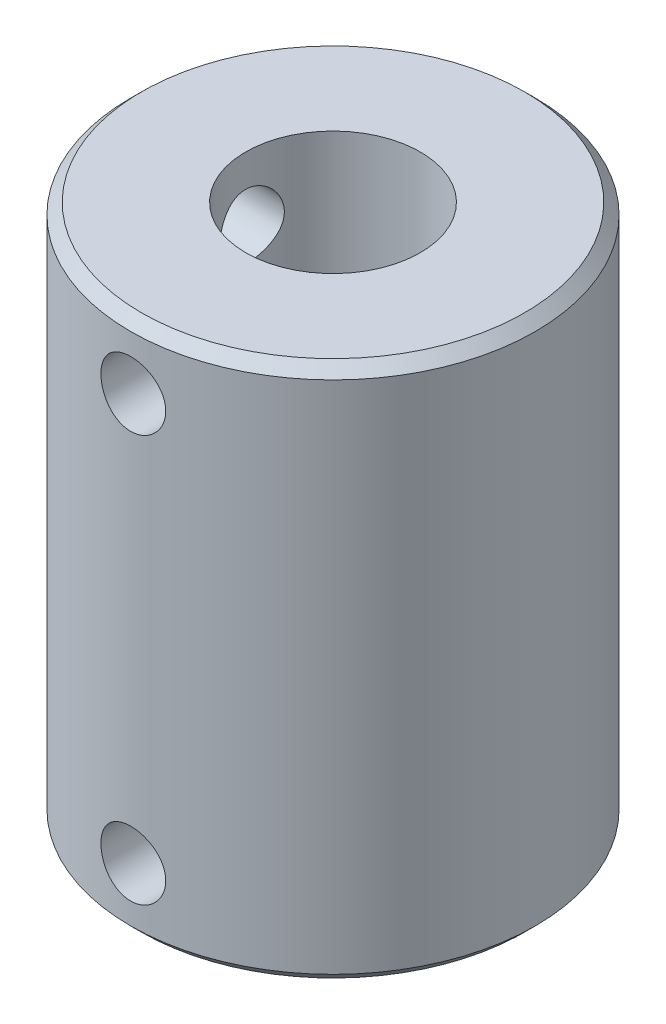
SolidWorks part; units mm, degrees
ref_plane "Front Plane" through (0, 0, 0) normal (0, 0, 1) x (1, 0, 0)
ref_plane "Top Plane" through (0, 0, 0) normal (0, 1, 0) x (1, 0, 0)
ref_plane "Right Plane" through (0, 0, 0) normal (1, 0, 0) x (0, 0, -1)
sketch "Sketch1" plane through (0, 0, 0) normal (0, 1, 0) x (1, 0, 0)
  circle A0 centre (0, 0) radius 9.36
  dimension "D1" = 18.72
extrude "Boss-Extrude1" add sketch "Sketch1" along normal blind 24.82
sketch "Sketch2" plane through (0, 0, 0) normal (0, 1, 0) x (1, 0, 0)
  circle A0 centre (0, 0) radius 2.545
  circle A1 centre (0, 0) radius 4.04
  dimension "D1" = 5.09
  dimension "D2" = 8.08
extrude "Cut-Extrude1" cut sketch "Sketch2" along normal through all contours A0 region at (0, 0, 0)
extrude "Cut-Extrude2" cut sketch "Sketch2<3>" against normal blind 18.28 from surface contours A1 A0 region at (-3.9257, 0, 0) starting at face at (0, 24.82, 2.545)
sketch "Sketch2<3>" plane through (0, 0, 0) normal (0, 1, 0) x (1, 0, 0) same geometry as "Sketch2"
chamfer "Chamfer1" distance 0.5 angle 45 2 edges at (0, 24.82, 9.36) (0, 0, 9.36)
sketch "Sketch3" plane through (0, 0, 0) normal (1, 0, 0) x (0, 0, -1)
  line L0 (0, 21.82) -> (0, 3) construction
  line L1 (9.36, 24.32) -> (9.36, 0.5) construction
  circle A0 centre (0, 21.82) radius 1.5
  circle A1 centre (0, 3) radius 1.5
  point P3 (9.36, 12.41)
  point P6 (0, 12.41)
  point P9 (0, 21.184)
  dimension "D1" = 3
  dimension "D2" = 3
extrude "Cut-Extrude3" cut sketch "Sketch3" against normal blind 18.28
pattern_circular "CirPattern1" count 2 over 90 about axis through (0, 24.82, 0) along (0, 1, 0) of "Cut-Extrude3"
